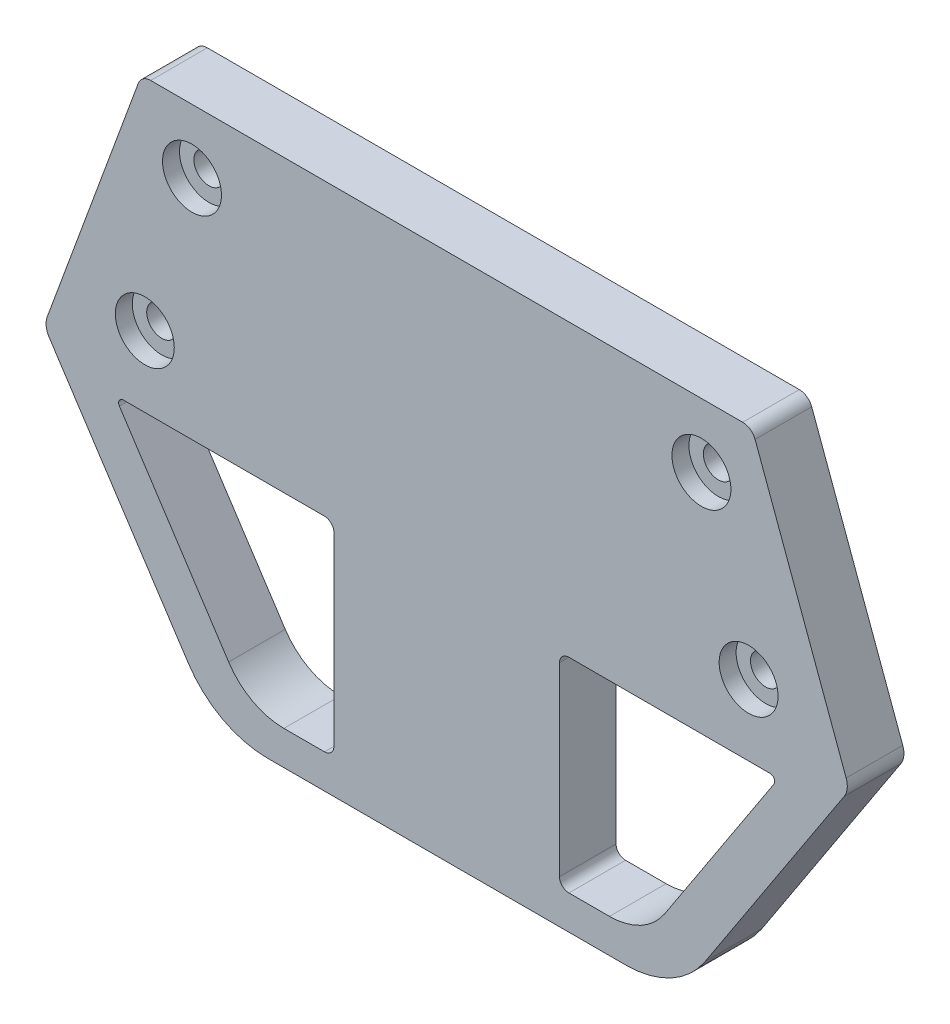
SolidWorks part; units mm, degrees
ref_plane "Front Plane" through (0, 0, 0) normal (0, 0, 1) x (1, 0, 0)
ref_plane "Top Plane" through (0, 0, 0) normal (0, 1, 0) x (1, 0, 0)
ref_plane "Right Plane" through (0, 0, 0) normal (1, 0, 0) x (0, 0, -1)
sketch "Sketch2" plane through (0, 0, 0) normal (0, 0, 1) x (1, 0, 0)
  line L0 (0, -56.4158) -> (0, 46.7895) construction
  line L3 (-53.7727, -0.3154) -> (-41.5133, 33.03)
  line L5 (-53.5141, -2.5826) -> (-34.7997, -31.1835)
  line L8 (-39.8446, 34.1945) -> (39.8446, 34.1945)
  line L9 (-24.13, -36.9528) -> (24.13, -36.9528)
  line L10 (53.5141, -2.5826) -> (34.7997, -31.1835)
  line L11 (53.7727, -0.3154) -> (41.5133, 33.03)
  arc A1 (-39.8446, 34.1945) -> (-41.5133, 33.03) centre (-39.8446, 32.4165) ccw
  arc A6 (-24.13, -36.9528) -> (-34.7997, -31.1835) centre (-24.13, -24.202) cw
  arc A8 (-53.5141, -2.5826) -> (-53.7727, -0.3154) centre (-51.3887, -1.1919) cw
  arc A10 (53.5141, -2.5826) -> (53.7727, -0.3154) centre (51.3887, -1.1919) ccw
  arc A11 (24.13, -36.9528) -> (34.7997, -31.1835) centre (24.13, -24.202) ccw
  arc A12 (39.8446, 34.1945) -> (41.5133, 33.03) centre (39.8446, 32.4165) cw
  point P4 (0, 57.6776)
  point P6 (54.2133, -1.514)
  point P7 (0, 34.1945)
  point P9 (0, 19.5776)
  point P19 (-31.0246, -36.9528)
  point P20 (0, -3.9055)
  point P24 (0, -36.9528)
  point P25 (31.0246, -36.9528)
  point P28 (-54.2133, -1.514)
extrude "Boss-Extrude1" add sketch "Sketch2" along normal blind 7.62
sketch "Sketch6" plane through (0, 0, 7.62) normal (0, 0, 1) x (1, 0, 0)
  line L0 (0, -25.1696) -> (0, 28.2164) construction
  line L3 (-44.0566, -5.8812) -> (-29.3539, -28.3511)
  line L4 (-53.5141, -2.5826) -> (-34.7997, -31.1835) construction
  line L5 (-53.9123, -1.4797) -> (0, -1.4797) construction
  line L6 (-43.5253, -4.8985) -> (-16.453, -4.8985)
  line L7 (-15.183, -6.1685) -> (-15.183, -31.1035)
  line L8 (-16.453, -32.3735) -> (-21.9149, -32.3735)
  line L9 (16.453, -32.3735) -> (21.9149, -32.3735)
  line L10 (15.183, -6.1685) -> (15.183, -31.1035)
  line L11 (43.5253, -4.8985) -> (16.453, -4.8985)
  line L12 (44.0566, -5.8812) -> (29.3539, -28.3511)
  line L15 (-11.43, -14.2874) -> (-11.43, -36.9528) construction
  line L16 (-24.13, -36.9528) -> (24.13, -36.9528) construction
  arc A3 (-53.7727, -0.3154) -> (-53.5141, -2.5826) centre (-51.3887, -1.1919) ccw construction
  arc A4 (-21.9149, -32.3735) -> (-29.3539, -28.3511) centre (-21.9149, -23.4835) cw
  arc A5 (-15.183, -31.1035) -> (-16.453, -32.3735) centre (-16.453, -31.1035) cw
  arc A6 (-15.183, -6.1685) -> (-16.453, -4.8985) centre (-16.453, -6.1685) ccw
  arc A7 (-43.5253, -4.8985) -> (-44.0566, -5.8812) centre (-43.5253, -5.5335) ccw
  arc A8 (43.5253, -4.8985) -> (44.0566, -5.8812) centre (43.5253, -5.5335) cw
  arc A9 (15.183, -6.1685) -> (16.453, -4.8985) centre (16.453, -6.1685) cw
  arc A10 (15.183, -31.1035) -> (16.453, -32.3735) centre (16.453, -31.1035) ccw
  arc A11 (21.9149, -32.3735) -> (29.3539, -28.3511) centre (21.9149, -23.4835) ccw
  dimension "D1" = 8.89
  dimension "D2" = 27.0723
  dimension "D3" = 15.183
  dimension "D4" = 0.635
  dimension "D8" = 1.27
  dimension "D5" = 26.8527
  dimension "D7" = 4.5793
  dimension "D9" = 22.6654
extrude "Cut-Extrude4" cut sketch "Sketch6" against normal through all
sketch "Sketch8" plane through (0, 0, 7.62) normal (0, 0, 1) x (1, 0, 0)
  line L0 (0, -16.6693) -> (0, 38.479) construction
  line L1 (-16.453, -4.8985) -> (-43.5253, -4.8985) construction
  circle A0 centre (-40.64, 4.6265) radius 2.032
  circle A1 centre (-34.29, 25.5815) radius 2.032
  circle A2 centre (40.64, 4.6265) radius 2.032
  circle A3 centre (34.29, 25.5815) radius 2.032
  dimension "D1" = 40.64
  dimension "D2" = 9.525
  dimension "D3" = 4.064
  dimension "D4" = 4.064
  dimension "D5" = 34.29
  dimension "D6" = 30.48
extrude "Cut-Extrude6" cut sketch "Sketch8" against normal through all
sketch "Sketch9" plane through (0, 0, 7.62) normal (0, 0, 1) x (1, 0, 0)
  line L0 (0, -13.6631) -> (0, 29.3567) construction
  circle A0 centre (-40.64, 4.6265) radius 3.9687
  circle A1 centre (-34.29, 25.5815) radius 3.9688
  circle A2 centre (40.64, 4.6265) radius 3.9687
  circle A3 centre (34.29, 25.5815) radius 3.9687
  dimension "D1" = 7.9375
  dimension "D2" = 7.9375
extrude "Cut-Extrude7" cut sketch "Sketch9" against normal blind 2.286
sketch "Sketch11" plane through (0, -36.9528, 0) normal (0, -1, 0) x (1, 0, 0)
  line L0 (0, 24.5167) -> (0, -10.8449) construction
  line L1 (-24.13, 3.81) -> (24.13, 3.81) construction
  line L2 (-24.13, 7.62) -> (-24.13, 0) construction
  line L3 (24.13, 7.62) -> (24.13, 0) construction
  circle A0 centre (0, 3.81) radius 2.032
  dimension "D1" = 4.064
extrude "Cut-Extrude9" cut sketch "Sketch11" against normal blind 25.4
